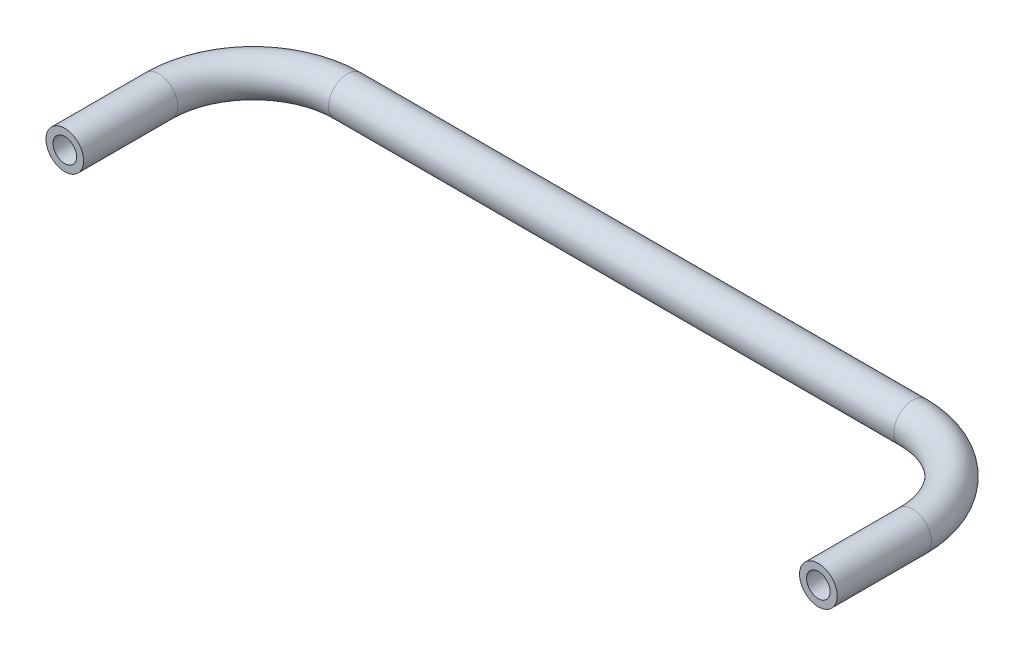
SolidWorks part; units mm, degrees
material "Chrome Stainless Steel"
ref_plane "Front Plane" through (0, 0, 0) normal (0, 0, 1) x (1, 0, 0)
ref_plane "Top Plane" through (0, 0, 0) normal (0, 1, 0) x (1, 0, 0)
ref_plane "Right Plane" through (0, 0, 0) normal (1, 0, 0) x (0, 0, -1)
sketch "Sketch1" plane through (0, 0, 0) normal (0, 1, 0) x (1, 0, 0)
  line L0 (-57.15, 0) -> (57.15, 0)
  line L1 (76.2, -19.05) -> (76.2, -38.1)
  line L2 (-76.2, -19.05) -> (-76.2, -38.1)
  arc A0 (-57.15, 0) -> (-76.2, -19.05) centre (-57.15, -19.05) ccw
  arc A1 (57.15, 0) -> (76.2, -19.05) centre (57.15, -19.05) cw
  point P8 (-76.2, 0)
  point P11 (76.2, 0)
  dimension "D3" = 19.05
  dimension "D4" = 19.05
  dimension "D1" = 152.4
  dimension "D2" = 38.1
ref_plane "Plane1" through (-76.2, 0, 38.1) normal (0, 0, 1) x (1, 0, 0)
sketch "Sketch2" plane through (-76.2, 0, 38.1) normal (0, 0, 1) x (1, 0, 0)
  circle A0 centre (0, 0) radius 3.81
  dimension "D1" = 7.62
sweep "Sweep1" add profiles "Sketch2" path "Sketch1"
hole_wizard "3/16 (0.1875) Diameter Hole1" positions "Sketch4" profile "Sketch3" hole size "3/16" standard "Ansi Inch"
sketch "Sketch4" plane through (0, 0, 38.1) normal (0, 0, 1) x (1, 0, 0)
  point P0 (-76.2, 0)
  point P1 (76.2, 0)
sketch "Sketch3" plane through (-76.2, 0, 38.1) normal (1, 0, 0) x (0, -1, 0)
  line L0 (0, 0) -> (0, 20.4808)
  line L1 (0, 20.4808) -> (2.3812, 19.05)
  line L2 (2.3812, 19.05) -> (2.3812, 0)
  line L5 (2.3812, 0) -> (0, 0)
  line L10 (0, 20.4808) -> (-2.3813, 19.05) construction
  line L11 (0, -6.35) -> (0, 107.95) construction
  dimension "Hole Dia." = 4.7625
  dimension "Hole Depth" = 19.05
  dimension "Drill Angle" = 118
